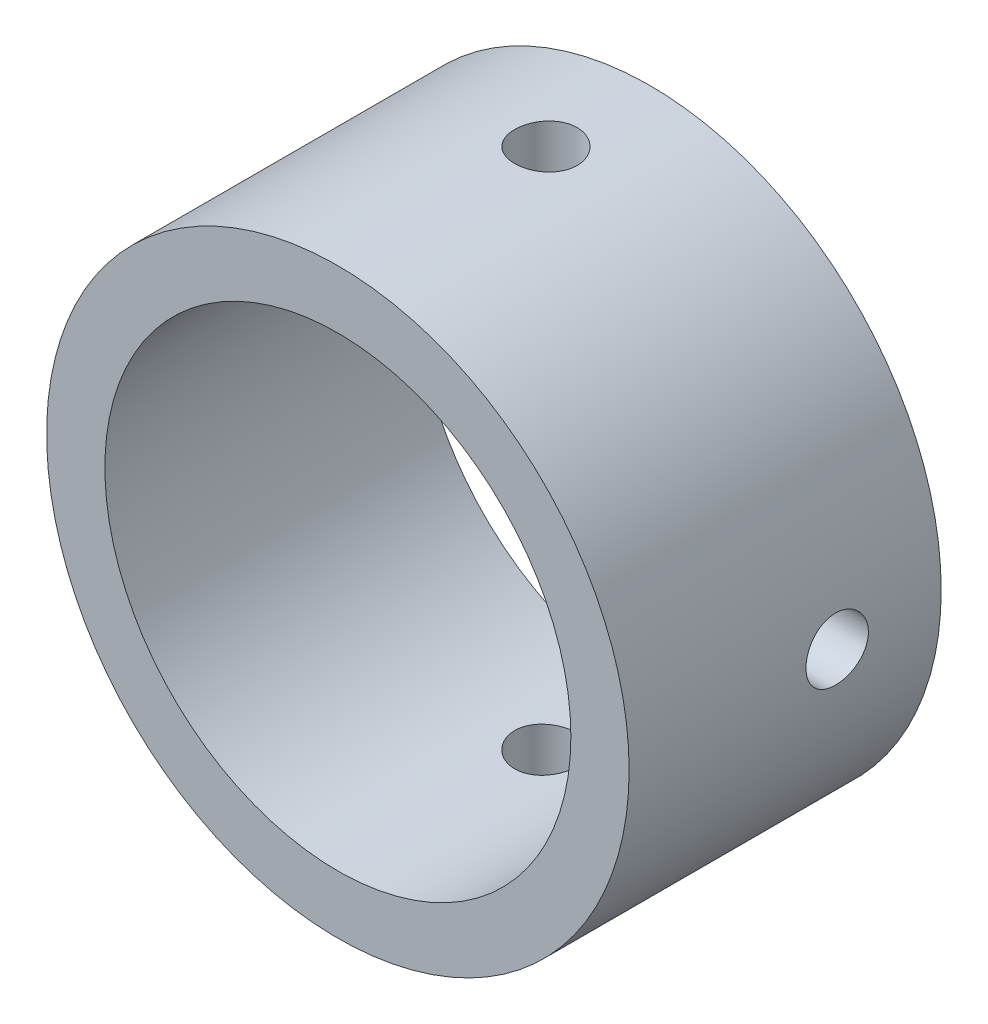
SolidWorks part; units mm, degrees
ref_plane "Front Plane" through (0, 0, 0) normal (0, 0, 1) x (1, 0, 0)
ref_plane "Top Plane" through (0, 0, 0) normal (0, 1, 0) x (1, 0, 0)
ref_plane "Right Plane" through (0, 0, 0) normal (1, 0, 0) x (0, 0, -1)
ref_axis "Z" through (0, 0, 10.75) along (0, 0, -1)
ref_axis "X" through (17.0818, 0, 0) along (-1, 0, 0)
ref_axis "Y" through (0, 15.4, 0) along (0, -1, 0)
sketch "Sketch1" plane through (0, 0, 0) normal (0, 0, 1) x (1, 0, 0)
  circle A0 centre (0, 0) radius 14
  circle A1 centre (0, 0) radius 11.2
  dimension "D1" = 28
  dimension "D2" = 22.4
extrude "Boss-Extrude1" add sketch "Sketch1" against normal blind 5 and the other way blind 10
sketch "Sketch2" plane through (0, 0, 0) normal (0, 1, 0) x (1, 0, 0)
  line L0 (-15.4, 0) -> (15.4, 0) construction
  line L1 (0, -8.25) -> (0, 8.25) construction
  circle A0 centre (0, 0) radius 1.5
  dimension "D1" = 3
extrude "Cut-Extrude1" cut sketch "Sketch2" against normal through all both and the other way through all
sketch "Sketch3" plane through (0, 0, 0) normal (1, 0, 0) x (0, 0, -1)
  circle A0 centre (0, 0) radius 1.5
  dimension "D1" = 3
extrude "Cut-Extrude2" cut sketch "Sketch3" along normal through all
equation "\"EyeDiameter\" = 28"
equation "\"BasePlaneDistance\" = 30"
equation "\"EyeClearance\" = 2"
equation "\"EyeOD\"= \"EyeDiameter\""
equation "\"D1@Sketch1\"=\"EyeOD\""
equation "\"D2@Sketch1\"=\"EyeDiameter\"*0.8"
equation "\"pinHoleDiameter\"= 3"
equation "\"D1@Sketch2\"=\"pinHoleDiameter\""
equation "\"D1@Sketch3\"=\"pinHoleDiameter\""
